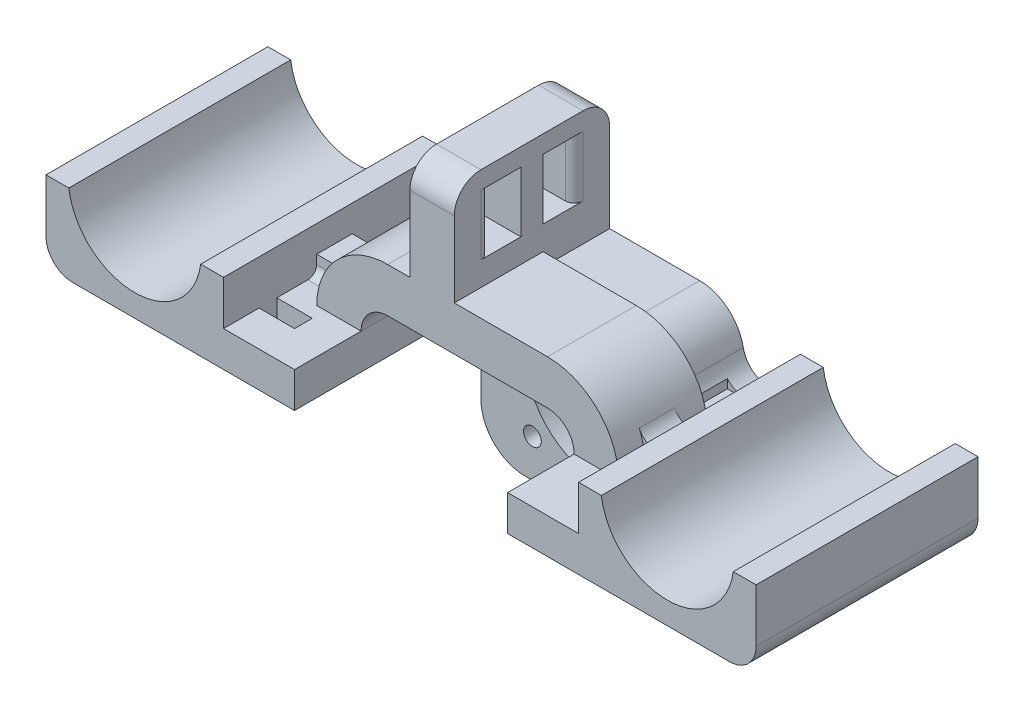
SolidWorks part; units mm, degrees
ref_plane "Plano frontal" through (0, 0, 0) normal (0, 0, 1) x (1, 0, 0)
ref_plane "Plano superior" through (0, 0, 0) normal (0, 1, 0) x (1, 0, 0)
ref_plane "Plano direito" through (0, 0, 0) normal (1, 0, 0) x (0, 0, -1)
sketch "Esboço1" plane through (0, 0, 0) normal (0, 1, 0) x (1, 0, 0)
  line L0 (-30, 0) -> (30, 0) construction
  line L1 (-40, 12.5) -> (40, 12.5)
  line L2 (-40, 12.5) -> (-40, -12.5)
  line L3 (-40, -12.5) -> (40, -12.5)
  line L4 (40, 12.5) -> (40, -12.5)
  line L5 (-40, 12.5) -> (40, -12.5) construction
  line L6 (-40, -12.5) -> (40, 12.5) construction
  point P0 (0, 0)
  point P9 (0, 0)
  dimension "D1" = 60
  dimension "D2" = 25
  dimension "D3" = 80
extrude "Ressalto-extrusão1" add sketch "Esboço1" along normal blind 4
sketch "Esboço2" plane through (0, 0, 12.5) normal (0, 0, 1) x (1, 0, 0)
  line L0 (30, 10) -> (-30, 10) construction
  line L2 (-40, 4) -> (40, 4) construction
  line L4 (0, 10) -> (0, 0) construction
  circle A0 centre (-30, 10) radius 7.5
  circle A1 centre (30, 10) radius 7.5
  point P5 (0, 10)
  dimension "D2" = 15
  dimension "D1" = 60
  dimension "D3" = 6
sketch "Esboço3" plane through (0, 0, 12.5) normal (0, 0, 1) x (1, 0, 0)
  line L0 (30, 10) -> (-30, 10) construction
  line L1 (-40, 4) -> (-20, 4)
  line L2 (-40, 4) -> (-40, 9)
  line L3 (-40, 9) -> (-20, 9)
  line L4 (-20, 4) -> (-20, 9)
  line L5 (40, 4) -> (20, 4)
  line L6 (40, 4) -> (40, 9)
  line L7 (40, 9) -> (20, 9)
  line L8 (20, 4) -> (20, 9)
  point P10 (30, 9)
  point P13 (-30, 9)
  dimension "D1" = 1
extrude "Ressalto-extrusão2" add sketch "Esboço3" against normal up to surface (25 mm away) up to face at (0, 2, -12.5)
sketch "Esboço4" plane through (0, 0, 12.5) normal (0, 0, 1) x (1, 0, 0)
  circle A0 centre (-30, 10) radius 7.5
  circle A1 centre (30, 10) radius 7.5
extrude "Corte-extrusão1" cut sketch "Esboço4" against normal up to surface (25 mm away) up to face at (0, 5.5, -12.5)
sketch "Esboço5" plane through (0, 4, 0) normal (0, 1, 0) x (1, 0, 0)
  line L0 (-18, 7.5) -> (-18, -7.5) construction
  line L1 (-20, 12.5) -> (-20, -12.5) construction
  line L2 (-20, 12.5) -> (-20, -12.5) construction
  line L3 (-16, 8.5) -> (-20, 8.5)
  line L4 (-16, 8.5) -> (-16, 6.5)
  line L5 (-16, 6.5) -> (-20, 6.5)
  line L6 (-20, 8.5) -> (-20, 6.5)
  line L7 (-16, 8.5) -> (-20, 6.5) construction
  line L8 (-16, 6.5) -> (-20, 8.5) construction
  line L9 (0, -6.5) -> (0, 6.5) construction
  line L10 (-8.3195, 0) -> (8.3195, 0) construction
  line L11 (-16, -6.5) -> (-20, -8.5) construction
  line L12 (-16, -8.5) -> (-20, -6.5) construction
  line L13 (-20, -8.5) -> (-20, -6.5)
  line L14 (-16, -6.5) -> (-20, -6.5)
  line L15 (-16, -8.5) -> (-16, -6.5)
  line L16 (-16, -8.5) -> (-20, -8.5)
  line L17 (16, -8.5) -> (20, -6.5) construction
  line L18 (16, -6.5) -> (20, -8.5) construction
  line L19 (16, -8.5) -> (20, -8.5)
  line L20 (16, -8.5) -> (16, -6.5)
  line L21 (16, -6.5) -> (20, -6.5)
  line L22 (20, -8.5) -> (20, -6.5)
  line L23 (16, 6.5) -> (20, 8.5) construction
  line L24 (16, 8.5) -> (20, 6.5) construction
  line L25 (20, 8.5) -> (20, 6.5)
  line L26 (16, 6.5) -> (20, 6.5)
  line L27 (16, 8.5) -> (16, 6.5)
  line L28 (16, 8.5) -> (20, 8.5)
  point P2 (-18, 0)
  point P5 (-20, 0)
  point P16 (0, 0)
  point P20 (0, 0)
  dimension "D1" = 2
  dimension "D2" = 15
  dimension "D3" = 2
extrude "Corte-extrusão2" cut sketch "Esboço5" against normal blind 5
fillet "Filete1" radius 3 2 edges at (-40, 0, 0) (40, 0, 0)
sketch "Esboço6" plane through (-20, 0, 0) normal (1, 0, 0) x (0, 0, -1)
  line L0 (6.5, 4) -> (-6.5, 4) construction
  line L1 (-2, 6) -> (2, 6)
  line L2 (-2, 6) -> (-2, 4)
  line L3 (-2, 4) -> (2, 4)
  line L4 (2, 6) -> (2, 4)
  line L5 (-2, 6) -> (2, 4) construction
  line L6 (-2, 4) -> (2, 6) construction
  point P0 (0, 5)
  point P12 (0, 4)
  point P13 (0, 4)
  dimension "D1" = 4
  dimension "D2" = 2
extrude "Ressalto-extrusão3" add sketch "Esboço6" along normal up to surface (40 mm away) up to face at (20, 3.5, 0)
fillet "Filete2" radius 1 2 edges at (0, 4, 2) (0, 4, -2)
sketch "Esboço10" plane through (0, 0, -12.5) normal (0, 0, -1) x (-1, 0, 0)
  line L1 (-13.5, 10.5) -> (13.5, 10.5)
  line L2 (-13.5, 10.5) -> (-13.5, -14.5)
  line L3 (-13.5, -14.5) -> (13.5, -14.5)
  line L4 (13.5, 10.5) -> (13.5, -14.5)
  line L5 (-13.5, 10.5) -> (13.5, -14.5) construction
  line L6 (-13.5, -14.5) -> (13.5, 10.5) construction
  line L7 (-37, 0) -> (37, 0) construction
  point P0 (0, -2)
  dimension "D1" = 25
  dimension "D2" = 2
  dimension "D3" = 27
extrude "Ressalto-extrusão4" add sketch "Esboço10" against normal blind 2.5
sketch "Esboço13" plane through (0, 0, -12.5) normal (0, 0, -1) x (-1, 0, 0)
  line L1 (-7.7, 3.7871) -> (7.7, 3.7871) construction
  line L2 (-7.7, 3.7871) -> (-7.7, -11.6129) construction
  line L3 (-7.7, -11.6129) -> (7.7, -11.6129) construction
  line L4 (7.7, 3.7871) -> (7.7, -11.6129) construction
  line L5 (-7.7, 3.7871) -> (7.7, -11.6129) construction
  line L6 (-7.7, -11.6129) -> (7.7, 3.7871) construction
  circle A0 centre (0, -3.9129) radius 8.5
  circle A1 centre (-7.7, 3.7871) radius 1
  circle A2 centre (7.7, 3.7871) radius 1
  circle A3 centre (7.7, -11.6129) radius 1
  circle A4 centre (-7.7, -11.6129) radius 1
  dimension "D1" = 2
  dimension "D3" = 17
  dimension "D2" = 15.4
extrude "Corte-extrusão3" cut sketch "Esboço13" against normal blind 5
sketch "Esboço14" plane through (0, 0, -10) normal (0, 0, 1) x (1, 0, 0)
  line L1 (-12, 8.0871) -> (12, 8.0871)
  line L2 (-12, 8.0871) -> (-12, -15.9129)
  line L3 (-12, -15.9129) -> (12, -15.9129)
  line L4 (12, 8.0871) -> (12, -15.9129)
  line L5 (-12, 8.0871) -> (12, -15.9129) construction
  line L6 (-12, -15.9129) -> (12, 8.0871) construction
  arc A0 (-7.5458, 0) -> (7.5458, 0) centre (0, -3.9129) ccw construction
  point P0 (0, -3.9129)
  point P5 (0, 0)
  dimension "D1" = 24
extrude "Corte-extrusão4" cut sketch "Esboço14" along normal blind 30
sketch "Esboço15" plane through (0, 4, 0) normal (0, 1, 0) x (1, 0, 0)
  line L0 (12, -3) -> (12, -12.5) construction
  line L1 (12, -5) -> (17, -5)
  line L2 (12, -5) -> (12, 5)
  line L3 (12, 5) -> (17, 5)
  line L4 (17, -5) -> (17, 5)
  line L5 (0, 0) -> (0, 10) construction
  line L6 (-13.5, 10) -> (13.5, 10) construction
  line L7 (-17, -5) -> (-17, 5)
  line L8 (-12, 5) -> (-17, 5)
  line L9 (-12, -5) -> (-12, 5)
  line L10 (-12, -5) -> (-17, -5)
  point P6 (17, 0)
  dimension "D1" = 5
  dimension "D2" = 10
extrude "Ressalto-extrusão5" add sketch "Esboço15" along normal blind 8
sketch "Esboço16" plane through (12, 0, 0) normal (-1, 0, 0) x (0, 0, 1)
  line L0 (5, 12) -> (5, 4) construction
  line L1 (-5, 12) -> (5, 12)
  line L2 (-5, 12) -> (-5, 7)
  line L3 (-5, 7) -> (5, 7)
  line L4 (5, 12) -> (5, 7)
  dimension "D1" = 5
extrude "Ressalto-extrusão6" add sketch "Esboço16" along normal up to surface (24 mm away) up to face at (-12, 5, 0.625)
fillet "Filete3" radius 3 2 edges at (12, 7, 0) (-12, 7, 0)
fillet "Filete4" radius 8 2 edges at (-17, 12, 0) (17, 12, 0)
fillet "Filete5" radius 2 2 edges at (16.746, 6, 0) (-16.746, 6, 0)
fillet "Filete6" radius 3 4 edges at (-13.5, 0, -11.25) (13.5, 0, -11.25) (13.5, 4, -11.25) (-13.5, 4, -11.25)
sketch "Esboço18" plane through (0, 0, -12.5) normal (0, 0, -1) x (-1, 0, 0)
  line L0 (13.5, -14.5) -> (13.5, -3) construction
  line L1 (-13.5, -14.5) -> (13.5, -14.5)
  line L2 (-13.5, -14.5) -> (-13.5, -15.9129)
  line L3 (-13.5, -15.9129) -> (13.5, -15.9129)
  line L4 (13.5, -14.5) -> (13.5, -15.9129)
  circle A0 centre (0, -3.9129) radius 8.5 construction
  point P7 (0, -3.9129)
  point P8 (0, 0)
  dimension "D1" = 12
extrude "Ressalto-extrusão7" add sketch "Esboço18" against normal up to surface (2.5 mm away) up to face at (0, 1, -10)
fillet "Filete7" radius 5 4 edges at (-13.5, -15.9129, -11.25) (13.5, -15.9129, -11.25) (-13.5, 10.5, -11.25) (13.5, 10.5, -11.25)
sketch "Esboço19" plane through (0, 0, -12.5) normal (0, 0, -1) x (-1, 0, 0)
  line L1 (8.6419, 10.5) -> (-8.6419, 10.5) construction
  line L2 (8.6419, 10.5) -> (-8.6419, 10.5)
  line L3 (9, 7) -> (-9, 7) construction
  line L4 (9, 7) -> (-9, 7)
  line L7 (0, 0) -> (0, 4.5871) construction
  line L8 (-12, 4) -> (-14.2639, 4)
  line L9 (-14.2639, 4) -> (-14.2639, 5)
  line L10 (12, 4) -> (14.2639, 4)
  line L11 (14.2639, 4) -> (14.2639, 5)
  arc A3 (-8.6419, 10.5) -> (-13.5532, 6.4375) centre (-8.6419, 5.5) ccw
  arc A4 (12, 4) -> (9, 7) centre (9, 4) ccw construction
  arc A5 (-9, 7) -> (-12, 4) centre (-9, 4) ccw construction
  arc A6 (12, 4) -> (9, 7) centre (9, 4) ccw
  arc A7 (-9, 7) -> (-12, 4) centre (-9, 4) ccw
  arc A8 (-14.2639, 5) -> (-13.5532, 6.4375) centre (-16.5, 7) ccw
  arc A9 (-16.5, 4) -> (-13.5532, 6.4375) centre (-16.5, 7) ccw construction
  circle A10 centre (0, -3.9129) radius 8.5 construction
  arc A12 (-8.6419, 10.5) -> (-13.5532, 6.4375) centre (-8.6419, 5.5) ccw construction
  arc A13 (8.6419, 10.5) -> (13.5532, 6.4375) centre (8.6419, 5.5) cw
  arc A14 (14.2639, 5) -> (13.5532, 6.4375) centre (16.5, 7) cw
  point P32 (-13.5169, 6.6823)
  point P33 (-13.5532, 7.5021)
  point P34 (-13.5532, 6.4375)
  point P35 (-13.5532, 6.3454)
  dimension "D1" = 1
extrude "Ressalto-extrusão8" add sketch "Esboço19" against normal up to surface (7.5 mm away) up to face at (0, 7.3195, -5)
sketch "Esboço20" plane through (0, 10.5, 0) normal (0, 1, 0) x (1, 0, 0)
  line L1 (-1.5, 12.5) -> (-6.5, 12.5)
  line L2 (-1.5, 12.5) -> (-1.5, -5)
  line L3 (-1.5, -5) -> (-6.5, -5)
  line L4 (-6.5, 12.5) -> (-6.5, -5)
  line L5 (-9, -5) -> (9, -5) construction
  dimension "D1" = 5
  dimension "D2" = 1.5
extrude "Ressalto-extrusão9" add sketch "Esboço20" along normal blind 13
sketch "Esboço21" plane through (-6.5, 0, 0) normal (-1, 0, 0) x (0, 0, 1)
  line L0 (-3.75, 23.5) -> (-3.75, 12) construction
  line L1 (-8.5, 21.5) -> (-5, 21.5)
  line L2 (-8.5, 21.5) -> (-8.5, 14.7)
  line L3 (-8.5, 14.7) -> (-5, 14.7)
  line L4 (-5, 21.5) -> (-5, 14.7)
  line L5 (-12.5, 23.5) -> (5, 23.5) construction
  line L6 (-5, 12) -> (5, 12) construction
  line L7 (-6.75, 18.1) -> (-3.75, 18.1) construction
  line L8 (-8.5, 21.5) -> (-5, 14.7) construction
  line L9 (-12.5, 23.5) -> (-12.5, 10.5) construction
  line L10 (-2.5, 21.5) -> (-2.5, 14.7)
  line L11 (1, 14.7) -> (-2.5, 14.7)
  line L12 (1, 21.5) -> (1, 14.7)
  line L13 (1, 21.5) -> (-2.5, 21.5)
  point P12 (0, 0)
  point P13 (-6.75, 18.1)
  point P14 (-8.3175, 16.5946)
  dimension "D1" = 3.5
  dimension "D2" = 6.8
  dimension "D3" = 2
  dimension "D4" = 4
extrude "Corte-extrusão6" cut sketch "Esboço21" against normal blind 10 and the other way blind 10
fillet "Filete9" radius 3 2 edges at (-4, 23.5, 5) (-4, 23.5, -12.5)
fillet "Filete10" radius 1 4 edges at (-6.5, 18.1, 1) (-6.5, 18.1, -8.5) (-1.5, 18.1, 1) (-1.5, 18.1, -8.5)
